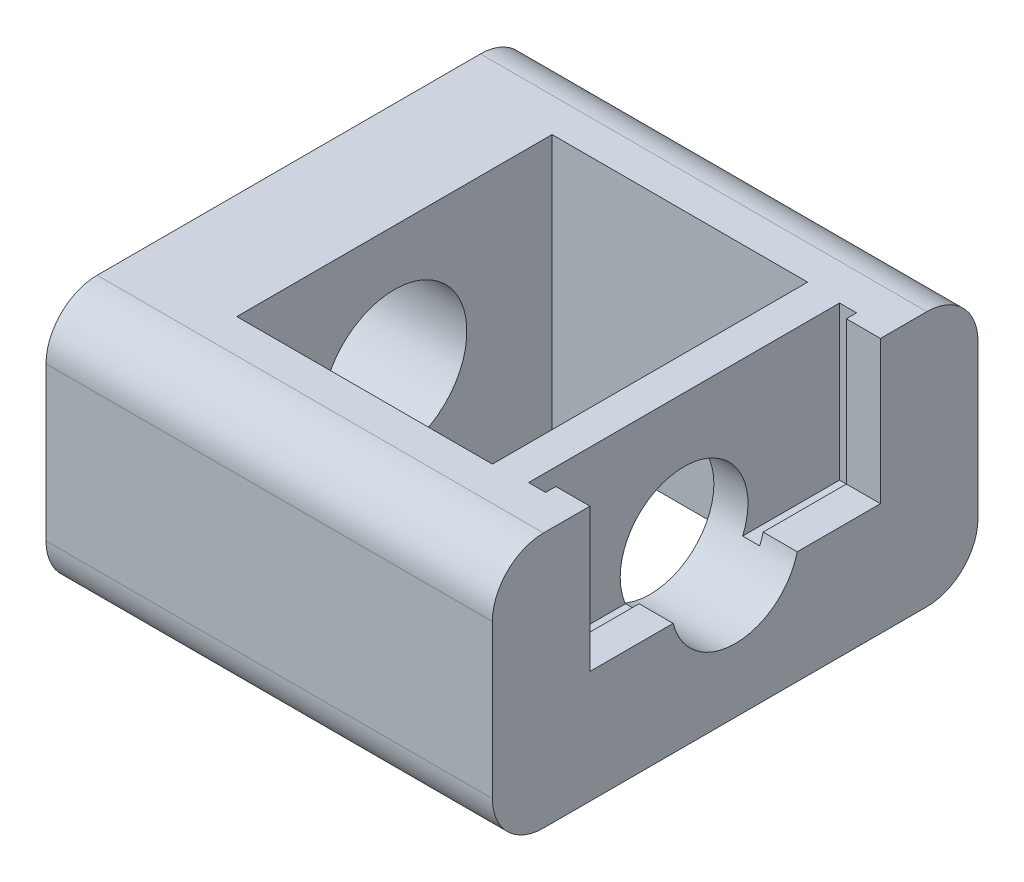
SolidWorks part; units mm, degrees
ref_plane "Front Plane" through (0, 0, 0) normal (0, 0, 1) x (1, 0, 0)
ref_plane "Top Plane" through (0, 0, 0) normal (0, 1, 0) x (1, 0, 0)
ref_plane "Right Plane" through (0, 0, 0) normal (1, 0, 0) x (0, 0, -1)
sketch "Sketch1" plane through (0, 0, 0) normal (1, 0, 0) x (0, 0, -1)
  line L1 (-14.25, -7.5) -> (14.25, -7.5)
  line L2 (-14.25, -7.5) -> (-14.25, 7.5)
  line L3 (-14.25, 7.5) -> (14.25, 7.5)
  line L4 (14.25, -7.5) -> (14.25, 7.5)
  line L5 (-14.25, -7.5) -> (14.25, 7.5) construction
  line L6 (-14.25, 7.5) -> (14.25, -7.5) construction
  circle A0 centre (0, 0) radius 4.25
  point P0 (0, 0)
  dimension "D3" = 8.5
  dimension "D1" = 28.5
  dimension "D2" = 15
extrude "Boss-Extrude1" add sketch "Sketch1" along normal blind 6.2
sketch "Sketch2" plane through (6.2, 0, 0) normal (1, 0, 0) x (0, 0, -1)
  line L0 (14.25, 7.5) -> (-14.25, 7.5) construction
  line L1 (-14.25, 7.5) -> (-9.25, 7.5)
  line L2 (-14.25, 7.5) -> (-14.25, -7.5)
  line L3 (-14.25, -7.5) -> (-9.25, -7.5)
  line L4 (-9.25, 7.5) -> (-9.25, -7.5)
  line L5 (-14.25, 7.5) -> (-9.25, -7.5) construction
  line L6 (-14.25, -7.5) -> (-9.25, 7.5) construction
  line L7 (-14.25, -7.5) -> (14.25, -7.5) construction
  line L8 (0, 0) -> (0, 50000) construction
  line L9 (14.25, -7.5) -> (9.25, -7.5)
  line L10 (9.25, 7.5) -> (9.25, -7.5)
  line L11 (14.25, 7.5) -> (9.25, 7.5)
  line L12 (14.25, 7.5) -> (14.25, -7.5)
  line L13 (-14.25, 7.5) -> (-14.25, -7.5) construction
  point P4 (-11.75, 0)
  point P12 (0, 7.5)
  dimension "D1" = 5
extrude "Boss-Extrude2" add sketch "Sketch2" along normal blind 15
sketch "Sketch3" plane through (21.2, 0, 0) normal (1, 0, 0) x (0, 0, -1)
  line L0 (0, 0) -> (0, 50000) construction
  line L1 (14.25, -7.5) -> (-14.25, -7.5)
  line L2 (14.25, -7.5) -> (14.25, 7.5)
  line L3 (14.25, 7.5) -> (-14.25, 7.5)
  line L4 (-14.25, -7.5) -> (-14.25, 7.5)
  line L5 (14.25, -7.5) -> (-14.25, 7.5) construction
  line L6 (14.25, 7.5) -> (-14.25, -7.5) construction
  line L7 (-8.525, 7.5) -> (-8.525, -0.9)
  line L8 (-9.125, -1.5) -> (9.125, -1.5)
  line L9 (-9.125, -1.5) -> (-9.125, 7.5)
  line L10 (-9.125, 7.5) -> (9.125, 7.5)
  line L11 (9.125, -1.5) -> (9.125, 7.5)
  line L12 (-9.125, -1.5) -> (9.125, 7.5) construction
  line L13 (-9.125, 7.5) -> (9.125, -1.5) construction
  line L14 (-8.525, -0.9) -> (8.525, -0.9)
  line L15 (8.525, -0.9) -> (8.525, 7.5)
  circle A0 centre (0, 0) radius 3.75
  point P4 (0, 0)
  point P9 (0, 3)
  line M9 (-14.25, 7.5) -> (-14.25, -7.5)
  line M10 (-14.25, -7.5) -> (-9.25, -7.5)
  line M11 (-9.25, -7.5) -> (-9.25, 7.5)
  line M12 (-9.25, 7.5) -> (-14.25, 7.5)
  dimension "D6" = 7.5
  dimension "D1" = 9
  dimension "D2" = 18.25
  dimension "D3" = 0.6
  dimension "D4" = 0.6
  dimension "D5" = 0.6
extrude "Boss-Extrude3" add sketch "Sketch3" along normal blind 5 contours M12 M9 M10 M11 | A0 L14 L15 L10 L7 | A0 L8 L9 L3 L1 L2 L11 M11 | A0 L14 L7 L3 L9 L8 | A0 L8 L11 L3 L15 L14 region at (21.2, -2.6295, -4.9759) region at (21.2, 0, 11.75) region at (21.2, 3, -9.0185) region at (21.2, 7.3935, 8.825) region at (21.2, 3.8487, 0)
extrude "Cut-Extrude2" cut sketch "Sketch3<6>" along normal blind 1 from offset 2 contours A0 L14 L15 L10 L7 | A0 L14 L7 L3 L9 L8 | A0 L8 L11 L3 L15 L14 region at (21.2, 3, -9.0185) region at (21.2, 7.3935, 8.825) region at (21.2, 3.8487, 0)
sketch "Sketch3<6>" plane through (21.2, 0, 0) normal (1, 0, 0) x (0, 0, -1) same geometry as "Sketch3"
extrude "Cut-Extrude3" cut sketch "Sketch3<7>" along normal through all from surface contours A0 L14 L15 L10 L7 region at (21.2, 3.8487, 0) starting at face at (23.2, 2.375, 0)
sketch "Sketch3<7>" plane through (21.2, 0, 0) normal (1, 0, 0) x (0, 0, -1) same geometry as "Sketch3"
fillet "Fillet1" radius 3 4 edges at (13.1, 7.5, 14.25) (13.1, -7.5, 14.25) (13.1, 7.5, -14.25) (13.1, -7.5, -14.25)
